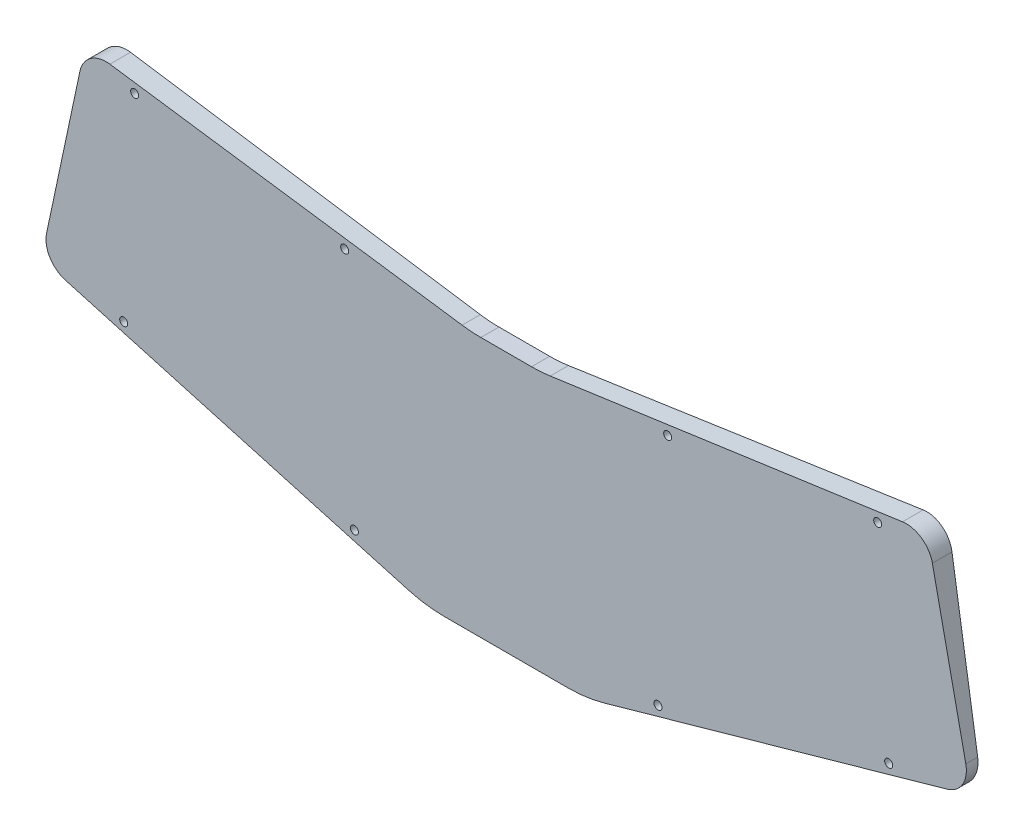
SolidWorks part; units mm, degrees
ref_plane "Front Plane" through (0, 0, 0) normal (0, 0, 1) x (1, 0, 0)
ref_plane "Top Plane" through (0, 0, 0) normal (0, 1, 0) x (1, 0, 0)
ref_plane "Right Plane" through (0, 0, 0) normal (1, 0, 0) x (0, 0, -1)
sketch "Model" plane through (0, 0, 0) normal (0, 0, 1) x (1, 0, 0)
  line L0 (325.3126, 39.9244) -> (319.5653, 66.9637)
  line L1 (325.3126, 39.9244) -> (332.0603, 8.179)
  line L2 (322.3782, 39.3007) -> (316.6308, 66.34)
  line L3 (322.3782, 39.3007) -> (329.1259, 7.5553)
  line L4 (306.4458, 71.4818) -> (308.8024, 71.8155)
  line L5 (13.8071, 71.4818) -> (11.4504, 71.8155)
  line L6 (-5.0598, 39.9244) -> (-11.8075, 8.179)
  line L7 (-2.1254, 39.3007) -> (-8.8731, 7.5553)
  line L8 (-5.0598, 39.9244) -> (0.6876, 66.9637)
  line L9 (-2.1254, 39.3007) -> (3.622, 66.34)
  line L10 (26.3327, -9.1816) -> (48.3039, -15.3856)
  line L11 (48.3039, -15.3856) -> (93.7705, -28.2242)
  line L12 (-3.9283, -0.6367) -> (7.4742, -3.8564)
  line L13 (90.0873, 60.6806) -> (30.9176, 69.0589)
  line L14 (210.7632, 57.9332) -> (177.0346, 53.1572)
  line L15 (169.604, 52.6338) -> (150.6488, 52.6338)
  line L16 (143.2182, 53.1572) -> (109.4896, 57.9332)
  line L17 (289.3352, 69.0589) -> (230.1656, 60.6806)
  line L18 (312.7787, -3.8564) -> (324.1811, -0.6367)
  line L19 (226.4824, -28.2242) -> (271.949, -15.3856)
  line L20 (271.949, -15.3856) -> (293.9202, -9.1816)
  line L21 (112.629, -33.5493) -> (124.2783, -36.8388)
  line L22 (137.0504, -38.6074) -> (160.1264, -38.6074)
  line L23 (160.1264, -38.6074) -> (183.2025, -38.6074)
  line L24 (195.9746, -36.8388) -> (207.6239, -33.5493)
  line L25 (169.604, 55.6338) -> (150.6488, 55.6338)
  line L26 (308.3818, 74.7858) -> (176.614, 56.1276)
  line L27 (272.7642, -18.2727) -> (324.9963, -3.5238)
  line L28 (196.7898, -39.7259) -> (272.7642, -18.2727)
  line L29 (160.1264, -41.6074) -> (183.2025, -41.6074)
  line L30 (137.0504, -41.6074) -> (160.1264, -41.6074)
  line L31 (47.4886, -18.2727) -> (123.463, -39.7259)
  line L32 (-4.7435, -3.5238) -> (47.4886, -18.2727)
  line L33 (143.6388, 56.1276) -> (11.8711, 74.7858)
  line L34 (196.5845, -32.4293) -> (202.5988, -29.3648)
  line L35 (190.1194, -20.2914) -> (196.2483, -32.32)
  line L36 (202.2573, -13.8263) -> (190.2287, -19.9552)
  line L37 (208.7224, -25.9641) -> (202.5935, -13.9355)
  line L38 (202.5988, -29.3648) -> (208.6131, -26.3004)
  line L39 (234.2278, -18.5408) -> (231.421, -5.3358)
  line L40 (220.8303, -21.6441) -> (234.0353, -18.8373)
  line L41 (217.7269, -8.2465) -> (220.5338, -21.4515)
  line L42 (231.1245, -5.1432) -> (217.9195, -7.95)
  line L43 (253.2284, -16.5467) -> (250.4216, -3.3417)
  line L44 (239.8309, -19.6501) -> (253.0359, -16.8433)
  line L45 (236.7276, -6.2525) -> (239.5344, -19.4575)
  line L46 (250.1251, -3.1492) -> (236.9201, -5.956)
  line L47 (210.4452, 1.9626) -> (207.6384, 15.1676)
  line L48 (197.0477, -1.1407) -> (210.2527, 1.6661)
  line L49 (193.9443, 12.2568) -> (196.7512, -0.9482)
  line L50 (207.3419, 15.3602) -> (194.1369, 12.5533)
  line L51 (206.4949, 20.5474) -> (203.6881, 33.7524)
  line L52 (193.0973, 17.4441) -> (206.3023, 20.2509)
  line L53 (189.994, 30.8416) -> (192.8008, 17.6366)
  line L54 (203.3916, 33.945) -> (190.1866, 31.1382)
  line L55 (202.5446, 39.1322) -> (199.7378, 52.3372)
  line L56 (189.147, 36.0289) -> (202.352, 38.8357)
  line L57 (186.0437, 49.4264) -> (188.8505, 36.2214)
  line L58 (199.4413, 52.5298) -> (186.2363, 49.723)
  line L59 (230.2775, 0.044) -> (227.4707, 13.249)
  line L60 (216.8799, -3.0593) -> (230.0849, -0.2525)
  line L61 (213.7766, 10.3383) -> (216.5834, -2.8667)
  line L62 (227.1742, 13.4416) -> (213.9692, 10.6348)
  line L63 (226.3272, 18.6288) -> (223.5204, 31.8338)
  line L64 (212.9296, 15.5255) -> (226.1346, 18.3323)
  line L65 (209.8263, 28.9231) -> (212.6331, 15.7181)
  line L66 (223.2239, 32.0264) -> (210.0189, 29.2196)
  line L67 (222.3769, 37.2136) -> (219.57, 50.4186)
  line L68 (208.9793, 34.1103) -> (222.1843, 36.9171)
  line L69 (205.876, 47.5079) -> (208.6828, 34.3029)
  line L70 (219.2735, 50.6112) -> (206.0685, 47.8044)
  line L71 (249.2781, 2.0381) -> (246.4713, 15.2431)
  line L72 (235.8806, -1.0653) -> (249.0856, 1.7416)
  line L73 (232.7772, 12.3323) -> (235.5841, -0.8727)
  line L74 (246.1748, 15.4356) -> (232.9698, 12.6288)
  line L75 (245.3278, 20.6229) -> (242.521, 33.8279)
  line L76 (231.9302, 17.5195) -> (245.1352, 20.3264)
  line L77 (228.8269, 30.9171) -> (231.6337, 17.7121)
  line L78 (242.2245, 34.0204) -> (229.0195, 31.2136)
  line L79 (241.3775, 39.2077) -> (238.5707, 52.4127)
  line L80 (227.9799, 36.1044) -> (241.1849, 38.9112)
  line L81 (224.8766, 49.5019) -> (227.6834, 36.2969)
  line L82 (238.2742, 52.6052) -> (225.0692, 49.7984)
  line L83 (271.2935, -10.151) -> (268.4867, 3.0539)
  line L84 (257.8959, -13.2544) -> (271.1009, -10.4476)
  line L85 (254.7926, 0.1432) -> (257.5994, -13.0618)
  line L86 (268.1901, 3.2465) -> (254.9852, 0.4397)
  line L87 (267.3431, 8.4338) -> (264.5363, 21.6387)
  line L88 (253.9456, 5.3304) -> (267.1506, 8.1372)
  line L89 (250.8423, 18.728) -> (253.6491, 5.523)
  line L90 (264.2398, 21.8313) -> (251.0348, 19.0245)
  line L91 (263.3928, 27.0186) -> (260.586, 40.2236)
  line L92 (249.9953, 23.9152) -> (263.2003, 26.722)
  line L93 (246.892, 37.3128) -> (249.6988, 24.1078)
  line L94 (260.2895, 40.4161) -> (247.0845, 37.6093)
  line L95 (259.4425, 45.6034) -> (256.6357, 58.8084)
  line L96 (246.045, 42.5) -> (259.2499, 45.3069)
  line L97 (242.9416, 55.8976) -> (245.7484, 42.6926)
  line L98 (256.3392, 59.0009) -> (243.1342, 56.1941)
  line L99 (286.4477, 9.9387) -> (283.6409, 23.1437)
  line L100 (273.0502, 6.8354) -> (286.2552, 9.6422)
  line L101 (269.9469, 20.2329) -> (272.7537, 7.0279)
  line L102 (283.3444, 23.3363) -> (270.1394, 20.5295)
  line L103 (282.4974, 28.5235) -> (279.6906, 41.7285)
  line L104 (269.0999, 25.4202) -> (282.3049, 28.227)
  line L105 (265.9965, 38.8177) -> (268.8033, 25.6128)
  line L106 (279.3941, 41.9211) -> (266.1891, 39.1143)
  line L107 (278.5471, 47.1083) -> (275.7403, 60.3133)
  line L108 (265.1495, 44.005) -> (278.3545, 46.8118)
  line L109 (262.0462, 57.4025) -> (264.853, 44.1976)
  line L110 (275.4438, 60.5059) -> (262.2388, 57.6991)
  line L111 (305.5523, 11.4437) -> (302.7455, 24.6487)
  line L112 (292.1548, 8.3403) -> (305.3598, 11.1471)
  line L113 (289.0514, 21.7379) -> (291.8582, 8.5329)
  line L114 (302.449, 24.8412) -> (289.244, 22.0344)
  line L115 (301.602, 30.0285) -> (298.7952, 43.2335)
  line L116 (288.2044, 26.9251) -> (301.4094, 29.732)
  line L117 (285.1011, 40.3227) -> (287.9079, 27.1177)
  line L118 (298.4987, 43.426) -> (285.2937, 40.6192)
  line L119 (297.6517, 48.6133) -> (294.8449, 61.8183)
  line L120 (284.2541, 45.5099) -> (297.4591, 48.3168)
  line L121 (281.1508, 58.9075) -> (283.9576, 45.7025)
  line L122 (294.5483, 62.0108) -> (281.3434, 59.204)
  line L123 (324.5529, 13.4377) -> (321.7461, 26.6427)
  line L124 (311.1554, 10.3344) -> (324.3604, 13.1412)
  line L125 (308.0521, 23.7319) -> (310.8589, 10.5269)
  line L126 (321.4496, 26.8352) -> (308.2446, 24.0284)
  line L127 (320.6026, 32.0225) -> (317.7958, 45.2275)
  line L128 (307.2051, 28.9192) -> (320.4101, 31.726)
  line L129 (304.1017, 42.3167) -> (306.9086, 29.1117)
  line L130 (317.4993, 45.42) -> (304.2943, 42.6132)
  line L131 (316.6523, 50.6073) -> (313.8455, 63.8123)
  line L132 (313.549, 64.0049) -> (300.344, 61.198)
  line L133 (300.1514, 60.9015) -> (302.9582, 47.6965)
  line L134 (303.2547, 47.504) -> (316.4597, 50.3108)
  line L135 (123.6683, -32.4293) -> (117.654, -29.3648)
  line L136 (130.1334, -20.2914) -> (124.0045, -32.32)
  line L137 (117.9956, -13.8263) -> (130.0242, -19.9552)
  line L138 (111.5305, -25.9641) -> (117.6593, -13.9355)
  line L139 (117.654, -29.3648) -> (111.6397, -26.3004)
  line L140 (86.025, -18.5408) -> (88.8318, -5.3358)
  line L141 (99.4226, -21.6441) -> (86.2176, -18.8373)
  line L142 (102.5259, -8.2465) -> (99.7191, -21.4515)
  line L143 (89.1283, -5.1432) -> (102.3333, -7.95)
  line L144 (67.0244, -16.5467) -> (69.8312, -3.3417)
  line L145 (80.4219, -19.6501) -> (67.2169, -16.8433)
  line L146 (83.5253, -6.2525) -> (80.7184, -19.4575)
  line L147 (70.1277, -3.1492) -> (83.3327, -5.956)
  line L148 (109.8076, 1.9626) -> (112.6144, 15.1676)
  line L149 (123.2052, -1.1407) -> (110.0002, 1.6661)
  line L150 (126.3085, 12.2568) -> (123.5017, -0.9482)
  line L151 (112.9109, 15.3602) -> (126.1159, 12.5533)
  line L152 (113.7579, 20.5474) -> (116.5647, 33.7524)
  line L153 (127.1555, 17.4441) -> (113.9505, 20.2509)
  line L154 (130.2588, 30.8416) -> (127.452, 17.6366)
  line L155 (116.8613, 33.945) -> (130.0662, 31.1382)
  line L156 (117.7083, 39.1322) -> (120.5151, 52.3372)
  line L157 (131.1058, 36.0289) -> (117.9008, 38.8357)
  line L158 (134.2091, 49.4264) -> (131.4023, 36.2214)
  line L159 (120.8116, 52.5298) -> (134.0166, 49.723)
  line L160 (89.9753, 0.044) -> (92.7821, 13.249)
  line L161 (103.3729, -3.0593) -> (90.1679, -0.2525)
  line L162 (106.4762, 10.3383) -> (103.6694, -2.8667)
  line L163 (93.0787, 13.4416) -> (106.2836, 10.6348)
  line L164 (93.9257, 18.6288) -> (96.7325, 31.8338)
  line L165 (107.3232, 15.5255) -> (94.1182, 18.3323)
  line L166 (110.4265, 28.9231) -> (107.6197, 15.7181)
  line L167 (97.029, 32.0264) -> (110.234, 29.2196)
  line L168 (97.876, 37.2136) -> (100.6828, 50.4186)
  line L169 (111.2735, 34.1103) -> (98.0685, 36.9171)
  line L170 (114.3769, 47.5079) -> (111.57, 34.3029)
  line L171 (100.9793, 50.6112) -> (114.1843, 47.8044)
  line L172 (70.9747, 2.0381) -> (73.7815, 15.2431)
  line L173 (84.3723, -1.0653) -> (71.1673, 1.7416)
  line L174 (87.4756, 12.3323) -> (84.6688, -0.8727)
  line L175 (74.078, 15.4356) -> (87.283, 12.6288)
  line L176 (74.925, 20.6229) -> (77.7318, 33.8279)
  line L177 (88.3226, 17.5195) -> (75.1176, 20.3264)
  line L178 (91.4259, 30.9171) -> (88.6191, 17.7121)
  line L179 (78.0284, 34.0204) -> (91.2333, 31.2136)
  line L180 (78.8753, 39.2077) -> (81.6822, 52.4127)
  line L181 (92.2729, 36.1044) -> (79.0679, 38.9112)
  line L182 (95.3762, 49.5019) -> (92.5694, 36.2969)
  line L183 (81.9787, 52.6052) -> (95.1837, 49.7984)
  line L184 (48.9594, -10.151) -> (51.7662, 3.0539)
  line L185 (62.3569, -13.2544) -> (49.1519, -10.4476)
  line L186 (65.4602, 0.1432) -> (62.6534, -13.0618)
  line L187 (52.0627, 3.2465) -> (65.2677, 0.4397)
  line L188 (52.9097, 8.4338) -> (55.7165, 21.6387)
  line L189 (66.3072, 5.3304) -> (53.1022, 8.1372)
  line L190 (69.4106, 18.728) -> (66.6037, 5.523)
  line L191 (56.013, 21.8313) -> (69.218, 19.0245)
  line L192 (56.86, 27.0186) -> (59.6668, 40.2236)
  line L193 (70.2576, 23.9152) -> (57.0526, 26.722)
  line L194 (73.3609, 37.3128) -> (70.5541, 24.1078)
  line L195 (59.9633, 40.4161) -> (73.1683, 37.6093)
  line L196 (60.8103, 45.6034) -> (63.6171, 58.8084)
  line L197 (74.2079, 42.5) -> (61.0029, 45.3069)
  line L198 (77.3112, 55.8976) -> (74.5044, 42.6926)
  line L199 (63.9136, 59.0009) -> (77.1186, 56.1941)
  line L200 (33.8051, 9.9387) -> (36.6119, 23.1437)
  line L201 (47.2026, 6.8354) -> (33.9977, 9.6422)
  line L202 (50.306, 20.2329) -> (47.4992, 7.0279)
  line L203 (36.9084, 23.3363) -> (50.1134, 20.5295)
  line L204 (37.7554, 28.5235) -> (40.5622, 41.7285)
  line L205 (51.153, 25.4202) -> (37.948, 28.227)
  line L206 (54.2563, 38.8177) -> (51.4495, 25.6128)
  line L207 (40.8587, 41.9211) -> (54.0637, 39.1143)
  line L208 (41.7057, 47.1083) -> (44.5125, 60.3133)
  line L209 (55.1033, 44.005) -> (41.8983, 46.8118)
  line L210 (58.2066, 57.4025) -> (55.3998, 44.1976)
  line L211 (44.8091, 60.5059) -> (58.0141, 57.6991)
  line L212 (14.7005, 11.4437) -> (17.5073, 24.6487)
  line L213 (28.0981, 8.3403) -> (14.8931, 11.1471)
  line L214 (31.2014, 21.7379) -> (28.3946, 8.5329)
  line L215 (17.8038, 24.8412) -> (31.0088, 22.0344)
  line L216 (18.6508, 30.0285) -> (21.4576, 43.2335)
  line L217 (32.0484, 26.9251) -> (18.8434, 29.732)
  line L218 (35.1517, 40.3227) -> (32.3449, 27.1177)
  line L219 (21.7542, 43.426) -> (34.9592, 40.6192)
  line L220 (22.6012, 48.6133) -> (25.408, 61.8183)
  line L221 (35.9987, 45.5099) -> (22.7937, 48.3168)
  line L222 (39.102, 58.9075) -> (36.2952, 45.7025)
  line L223 (25.7045, 62.0108) -> (38.9095, 59.204)
  line L224 (-4.3001, 13.4377) -> (-1.4933, 26.6427)
  line L225 (9.0974, 10.3344) -> (-4.1076, 13.1412)
  line L226 (12.2008, 23.7319) -> (9.394, 10.5269)
  line L227 (-1.1968, 26.8352) -> (12.0082, 24.0284)
  line L228 (-0.3498, 32.0225) -> (2.457, 45.2275)
  line L229 (13.0478, 28.9192) -> (-0.1572, 31.726)
  line L230 (16.1511, 42.3167) -> (13.3443, 29.1117)
  line L231 (2.7535, 45.42) -> (15.9585, 42.6132)
  line L232 (3.6005, 50.6073) -> (6.4073, 63.8123)
  line L233 (6.7039, 64.0049) -> (19.9088, 61.198)
  line L234 (20.1014, 60.9015) -> (17.2946, 47.6965)
  line L235 (16.9981, 47.504) -> (3.7931, 50.3108)
  circle A0 centre (21.1464, 69.9376) radius 1.5
  circle A1 centre (299.1065, 69.9376) radius 1.5
  arc A2 (296.6652, 67.2112) -> (289.3352, 69.0589) centre (290.7372, 59.1577) ccw
  arc A3 (306.4458, 71.4818) -> (302.641, 68.6986) centre (307.1468, 66.5312) ccw
  arc A4 (17.6118, 68.6986) -> (13.8071, 71.4818) centre (13.106, 66.5312) ccw
  arc A5 (30.9176, 69.0589) -> (23.5876, 67.2112) centre (29.5156, 59.1577) ccw
  arc A6 (17.6118, 68.6986) -> (23.5876, 67.2112) centre (21.2165, 70.4326) ccw
  arc A7 (296.6652, 67.2112) -> (302.641, 68.6986) centre (299.0364, 70.4326) ccw
  arc A8 (324.9963, -3.5238) -> (332.0603, 8.179) centre (322.2789, 6.0999) ccw
  arc A9 (319.5653, 66.9637) -> (308.3818, 74.7858) centre (309.7838, 64.8846) ccw
  arc A10 (324.1811, -0.6367) -> (329.1259, 7.5553) centre (322.2789, 6.0999) ccw
  arc A11 (316.6308, 66.34) -> (308.8024, 71.8155) centre (309.7838, 64.8846) ccw
  arc A12 (11.8711, 74.7858) -> (0.6876, 66.9637) centre (10.469, 64.8846) ccw
  arc A13 (-11.8075, 8.179) -> (-4.7435, -3.5238) centre (-2.026, 6.0999) ccw
  arc A14 (-8.8731, 7.5553) -> (-3.9283, -0.6367) centre (-2.026, 6.0999) ccw
  arc A15 (11.4504, 71.8155) -> (3.622, 66.34) centre (10.469, 64.8846) ccw
  circle A16 centre (303.2135, -6.0378) radius 1.5
  circle A17 centre (17.0393, -6.0378) radius 1.5
  arc A18 (293.9202, -9.1816) -> (299.8789, -4.5301) centre (291.2027, 0.4421) ccw
  arc A19 (305.2671, -3.0086) -> (312.7787, -3.8564) centre (310.0612, 5.7673) ccw
  arc A20 (20.3739, -4.5301) -> (26.3327, -9.1816) centre (29.0501, 0.4421) ccw
  arc A21 (7.4742, -3.8564) -> (14.9858, -3.0086) centre (10.1916, 5.7673) ccw
  arc A22 (20.3739, -4.5301) -> (14.9858, -3.0086) centre (16.9034, -6.519) ccw
  arc A23 (305.2671, -3.0086) -> (299.8789, -4.5301) centre (303.3494, -6.519) ccw
  circle A24 centre (220.5345, 58.8118) radius 1.5
  circle A25 centre (99.7183, 58.8118) radius 1.5
  arc A26 (230.1656, 60.6806) -> (223.6367, 56.8704) centre (231.5676, 50.7793) ccw
  arc A27 (218.0932, 56.0855) -> (210.7632, 57.9332) centre (212.1652, 48.032) ccw
  arc A28 (96.6161, 56.8704) -> (90.0873, 60.6806) centre (88.6852, 50.7793) ccw
  arc A29 (109.4896, 57.9332) -> (102.1596, 56.0855) centre (108.0876, 48.032) ccw
  arc A30 (218.0932, 56.0855) -> (223.6367, 56.8704) centre (220.4644, 59.3069) ccw
  arc A31 (96.6161, 56.8704) -> (102.1596, 56.0855) centre (99.7884, 59.3069) ccw
  circle A32 centre (216.9173, -30.4056) radius 1.5
  arc A33 (218.9708, -27.3764) -> (226.4824, -28.2242) centre (223.7649, -18.6005) ccw
  arc A34 (207.6239, -33.5493) -> (213.5826, -28.8979) centre (204.9064, -23.9256) ccw
  circle A35 centre (103.3356, -30.4056) radius 1.5
  arc A36 (106.6702, -28.8979) -> (112.629, -33.5493) centre (115.3464, -23.9256) ccw
  arc A37 (93.7705, -28.2242) -> (101.2821, -27.3764) centre (96.4879, -18.6005) ccw
  arc A38 (218.9708, -27.3764) -> (213.5826, -28.8979) centre (217.0531, -30.8868) ccw
  arc A39 (106.6702, -28.8979) -> (101.2821, -27.3764) centre (103.1997, -30.8868) ccw
  arc A40 (169.604, 55.6338) -> (176.614, 56.1276) centre (169.604, 105.6338) ccw
  arc A41 (183.2025, -41.6074) -> (196.7898, -39.7259) centre (183.2025, 8.3926) ccw
  arc A42 (123.463, -39.7259) -> (137.0504, -41.6074) centre (137.0504, 8.3926) ccw
  arc A43 (143.6388, 56.1276) -> (150.6488, 55.6338) centre (150.6488, 105.6338) ccw
  arc A44 (196.2483, -32.32) -> (196.5845, -32.4293) centre (196.471, -32.2065) ccw
  arc A45 (190.2287, -19.9552) -> (190.1194, -20.2914) centre (190.3422, -20.1779) ccw
  arc A46 (202.5935, -13.9355) -> (202.2573, -13.8263) centre (202.3708, -14.049) ccw
  arc A47 (208.6131, -26.3004) -> (208.7224, -25.9641) centre (208.4996, -26.0776) ccw
  arc A48 (231.421, -5.3358) -> (231.1245, -5.1432) centre (231.1765, -5.3878) ccw
  arc A49 (217.9195, -7.95) -> (217.7269, -8.2465) centre (217.9715, -8.1946) ccw
  arc A50 (220.5338, -21.4515) -> (220.8303, -21.6441) centre (220.7783, -21.3996) ccw
  arc A51 (234.0353, -18.8373) -> (234.2278, -18.5408) centre (233.9833, -18.5927) ccw
  arc A52 (250.4216, -3.3417) -> (250.1251, -3.1492) centre (250.1771, -3.3937) ccw
  arc A53 (236.9201, -5.956) -> (236.7276, -6.2525) centre (236.9721, -6.2005) ccw
  arc A54 (239.5344, -19.4575) -> (239.8309, -19.6501) centre (239.7789, -19.4055) ccw
  arc A55 (253.0359, -16.8433) -> (253.2284, -16.5467) centre (252.9839, -16.5987) ccw
  arc A56 (207.6384, 15.1676) -> (207.3419, 15.3602) centre (207.3939, 15.1156) ccw
  arc A57 (194.1369, 12.5533) -> (193.9443, 12.2568) centre (194.1889, 12.3088) ccw
  arc A58 (196.7512, -0.9482) -> (197.0477, -1.1407) centre (196.9957, -0.8962) ccw
  arc A59 (210.2527, 1.6661) -> (210.4452, 1.9626) centre (210.2007, 1.9106) ccw
  arc A60 (203.6881, 33.7524) -> (203.3916, 33.945) centre (203.4436, 33.7004) ccw
  arc A61 (190.1866, 31.1382) -> (189.994, 30.8416) centre (190.2386, 30.8936) ccw
  arc A62 (192.8008, 17.6366) -> (193.0973, 17.4441) centre (193.0454, 17.6886) ccw
  arc A63 (206.3023, 20.2509) -> (206.4949, 20.5474) centre (206.2504, 20.4954) ccw
  arc A64 (199.7378, 52.3372) -> (199.4413, 52.5298) centre (199.4932, 52.2852) ccw
  arc A65 (186.2363, 49.723) -> (186.0437, 49.4264) centre (186.2882, 49.4784) ccw
  arc A66 (188.8505, 36.2214) -> (189.147, 36.0289) centre (189.095, 36.2734) ccw
  arc A67 (202.352, 38.8357) -> (202.5446, 39.1322) centre (202.3, 39.0802) ccw
  arc A68 (227.4707, 13.249) -> (227.1742, 13.4416) centre (227.2262, 13.1971) ccw
  arc A69 (213.9692, 10.6348) -> (213.7766, 10.3383) centre (214.0212, 10.3902) ccw
  arc A70 (216.5834, -2.8667) -> (216.8799, -3.0593) centre (216.828, -2.8147) ccw
  arc A71 (230.0849, -0.2525) -> (230.2775, 0.044) centre (230.033, -0.0079) ccw
  arc A72 (223.5204, 31.8338) -> (223.2239, 32.0264) centre (223.2758, 31.7819) ccw
  arc A73 (210.0189, 29.2196) -> (209.8263, 28.9231) centre (210.0708, 28.9751) ccw
  arc A74 (212.6331, 15.7181) -> (212.9296, 15.5255) centre (212.8776, 15.7701) ccw
  arc A75 (226.1346, 18.3323) -> (226.3272, 18.6288) centre (226.0826, 18.5769) ccw
  arc A76 (219.57, 50.4186) -> (219.2735, 50.6112) centre (219.3255, 50.3667) ccw
  arc A77 (206.0685, 47.8044) -> (205.876, 47.5079) centre (206.1205, 47.5599) ccw
  arc A78 (208.6828, 34.3029) -> (208.9793, 34.1103) centre (208.9273, 34.3549) ccw
  arc A79 (222.1843, 36.9171) -> (222.3769, 37.2136) centre (222.1323, 37.1617) ccw
  arc A80 (246.4713, 15.2431) -> (246.1748, 15.4356) centre (246.2268, 15.1911) ccw
  arc A81 (249.0856, 1.7416) -> (249.2781, 2.0381) centre (249.0336, 1.9861) ccw
  arc A82 (232.9698, 12.6288) -> (232.7772, 12.3323) centre (233.0218, 12.3843) ccw
  arc A83 (235.5841, -0.8727) -> (235.8806, -1.0653) centre (235.8286, -0.8207) ccw
  arc A84 (242.521, 33.8279) -> (242.2245, 34.0204) centre (242.2765, 33.7759) ccw
  arc A85 (229.0195, 31.2136) -> (228.8269, 30.9171) centre (229.0715, 30.9691) ccw
  arc A86 (231.6337, 17.7121) -> (231.9302, 17.5195) centre (231.8783, 17.7641) ccw
  arc A87 (245.1352, 20.3264) -> (245.3278, 20.6229) centre (245.0833, 20.5709) ccw
  arc A88 (238.5707, 52.4127) -> (238.2742, 52.6052) centre (238.3261, 52.3607) ccw
  arc A89 (225.0692, 49.7984) -> (224.8766, 49.5019) centre (225.1211, 49.5539) ccw
  arc A90 (227.6834, 36.2969) -> (227.9799, 36.1044) centre (227.9279, 36.3489) ccw
  arc A91 (241.1849, 38.9112) -> (241.3775, 39.2077) centre (241.1329, 39.1557) ccw
  arc A92 (268.4867, 3.0539) -> (268.1901, 3.2465) centre (268.2421, 3.002) ccw
  arc A93 (254.9852, 0.4397) -> (254.7926, 0.1432) centre (255.0371, 0.1952) ccw
  arc A94 (257.5994, -13.0618) -> (257.8959, -13.2544) centre (257.8439, -13.0098) ccw
  arc A95 (271.1009, -10.4476) -> (271.2935, -10.151) centre (271.0489, -10.203) ccw
  arc A96 (264.5363, 21.6387) -> (264.2398, 21.8313) centre (264.2918, 21.5868) ccw
  arc A97 (251.0348, 19.0245) -> (250.8423, 18.728) centre (251.0868, 18.78) ccw
  arc A98 (253.6491, 5.523) -> (253.9456, 5.3304) centre (253.8936, 5.575) ccw
  arc A99 (267.1506, 8.1372) -> (267.3431, 8.4338) centre (267.0986, 8.3818) ccw
  arc A100 (260.586, 40.2236) -> (260.2895, 40.4161) centre (260.3415, 40.1716) ccw
  arc A101 (247.0845, 37.6093) -> (246.892, 37.3128) centre (247.1365, 37.3648) ccw
  arc A102 (249.6988, 24.1078) -> (249.9953, 23.9152) centre (249.9433, 24.1598) ccw
  arc A103 (263.2003, 26.722) -> (263.3928, 27.0186) centre (263.1483, 26.9666) ccw
  arc A104 (256.6357, 58.8084) -> (256.3392, 59.0009) centre (256.3912, 58.7564) ccw
  arc A105 (243.1342, 56.1941) -> (242.9416, 55.8976) centre (243.1862, 55.9496) ccw
  arc A106 (245.7484, 42.6926) -> (246.045, 42.5) centre (245.993, 42.7446) ccw
  arc A107 (259.2499, 45.3069) -> (259.4425, 45.6034) centre (259.198, 45.5514) ccw
  arc A108 (283.6409, 23.1437) -> (283.3444, 23.3363) centre (283.3964, 23.0917) ccw
  arc A109 (270.1394, 20.5295) -> (269.9469, 20.2329) centre (270.1914, 20.2849) ccw
  arc A110 (272.7537, 7.0279) -> (273.0502, 6.8354) centre (272.9982, 7.0799) ccw
  arc A111 (286.2552, 9.6422) -> (286.4477, 9.9387) centre (286.2032, 9.8867) ccw
  arc A112 (279.6906, 41.7285) -> (279.3941, 41.9211) centre (279.4461, 41.6765) ccw
  arc A113 (266.1891, 39.1143) -> (265.9965, 38.8177) centre (266.2411, 38.8697) ccw
  arc A114 (268.8033, 25.6128) -> (269.0999, 25.4202) centre (269.0479, 25.6647) ccw
  arc A115 (282.3049, 28.227) -> (282.4974, 28.5235) centre (282.2529, 28.4715) ccw
  arc A116 (275.7403, 60.3133) -> (275.4438, 60.5059) centre (275.4957, 60.2613) ccw
  arc A117 (262.2388, 57.6991) -> (262.0462, 57.4025) centre (262.2908, 57.4545) ccw
  arc A118 (264.853, 44.1976) -> (265.1495, 44.005) centre (265.0976, 44.2495) ccw
  arc A119 (278.3545, 46.8118) -> (278.5471, 47.1083) centre (278.3026, 47.0563) ccw
  arc A120 (302.7455, 24.6487) -> (302.449, 24.8412) centre (302.501, 24.5967) ccw
  arc A121 (305.3598, 11.1471) -> (305.5523, 11.4437) centre (305.3078, 11.3917) ccw
  arc A122 (289.244, 22.0344) -> (289.0514, 21.7379) centre (289.296, 21.7899) ccw
  arc A123 (291.8582, 8.5329) -> (292.1548, 8.3403) centre (292.1028, 8.5849) ccw
  arc A124 (298.7952, 43.2335) -> (298.4987, 43.426) centre (298.5506, 43.1815) ccw
  arc A125 (285.2937, 40.6192) -> (285.1011, 40.3227) centre (285.3457, 40.3747) ccw
  arc A126 (287.9079, 27.1177) -> (288.2044, 26.9251) centre (288.1525, 27.1697) ccw
  arc A127 (301.4094, 29.732) -> (301.602, 30.0285) centre (301.3575, 29.9765) ccw
  arc A128 (294.8449, 61.8183) -> (294.5483, 62.0108) centre (294.6003, 61.7663) ccw
  arc A129 (281.3434, 59.204) -> (281.1508, 58.9075) centre (281.3953, 58.9595) ccw
  arc A130 (283.9576, 45.7025) -> (284.2541, 45.5099) centre (284.2021, 45.7545) ccw
  arc A131 (297.4591, 48.3168) -> (297.6517, 48.6133) centre (297.4071, 48.5613) ccw
  arc A132 (321.7461, 26.6427) -> (321.4496, 26.8352) centre (321.5016, 26.5907) ccw
  arc A133 (308.2446, 24.0284) -> (308.0521, 23.7319) centre (308.2966, 23.7839) ccw
  arc A134 (310.8589, 10.5269) -> (311.1554, 10.3344) centre (311.1034, 10.5789) ccw
  arc A135 (324.3604, 13.1412) -> (324.5529, 13.4377) centre (324.3084, 13.3857) ccw
  arc A136 (317.7958, 45.2275) -> (317.4993, 45.42) centre (317.5513, 45.1755) ccw
  arc A137 (306.9086, 29.1117) -> (307.2051, 28.9192) centre (307.1531, 29.1637) ccw
  arc A138 (320.4101, 31.726) -> (320.6026, 32.0225) centre (320.3581, 31.9705) ccw
  arc A139 (304.2943, 42.6132) -> (304.1017, 42.3167) centre (304.3463, 42.3687) ccw
  arc A140 (313.8455, 63.8123) -> (313.549, 64.0049) centre (313.601, 63.7603) ccw
  arc A141 (300.344, 61.198) -> (300.1514, 60.9015) centre (300.396, 60.9535) ccw
  arc A142 (316.4597, 50.3108) -> (316.6523, 50.6073) centre (316.4078, 50.5553) ccw
  arc A143 (302.9582, 47.6965) -> (303.2547, 47.504) centre (303.2028, 47.7485) ccw
  arc A144 (123.6683, -32.4293) -> (124.0045, -32.32) centre (123.7818, -32.2065) ccw
  arc A145 (130.1334, -20.2914) -> (130.0242, -19.9552) centre (129.9107, -20.1779) ccw
  arc A146 (117.9956, -13.8263) -> (117.6593, -13.9355) centre (117.8821, -14.049) ccw
  arc A147 (111.5305, -25.9641) -> (111.6397, -26.3004) centre (111.7532, -26.0776) ccw
  arc A148 (89.1283, -5.1432) -> (88.8318, -5.3358) centre (89.0764, -5.3878) ccw
  arc A149 (102.5259, -8.2465) -> (102.3333, -7.95) centre (102.2813, -8.1946) ccw
  arc A150 (99.4226, -21.6441) -> (99.7191, -21.4515) centre (99.4745, -21.3996) ccw
  arc A151 (86.025, -18.5408) -> (86.2176, -18.8373) centre (86.2695, -18.5927) ccw
  arc A152 (70.1277, -3.1492) -> (69.8312, -3.3417) centre (70.0757, -3.3937) ccw
  arc A153 (83.5253, -6.2525) -> (83.3327, -5.956) centre (83.2807, -6.2005) ccw
  arc A154 (80.4219, -19.6501) -> (80.7184, -19.4575) centre (80.4739, -19.4055) ccw
  arc A155 (67.0244, -16.5467) -> (67.2169, -16.8433) centre (67.2689, -16.5987) ccw
  arc A156 (112.9109, 15.3602) -> (112.6144, 15.1676) centre (112.859, 15.1156) ccw
  arc A157 (126.3085, 12.2568) -> (126.1159, 12.5533) centre (126.0639, 12.3088) ccw
  arc A158 (123.2052, -1.1407) -> (123.5017, -0.9482) centre (123.2571, -0.8962) ccw
  arc A159 (109.8076, 1.9626) -> (110.0002, 1.6661) centre (110.0521, 1.9106) ccw
  arc A160 (116.8613, 33.945) -> (116.5647, 33.7524) centre (116.8093, 33.7004) ccw
  arc A161 (130.2588, 30.8416) -> (130.0662, 31.1382) centre (130.0143, 30.8936) ccw
  arc A162 (127.1555, 17.4441) -> (127.452, 17.6366) centre (127.2075, 17.6886) ccw
  arc A163 (113.7579, 20.5474) -> (113.9505, 20.2509) centre (114.0025, 20.4954) ccw
  arc A164 (120.8116, 52.5298) -> (120.5151, 52.3372) centre (120.7596, 52.2852) ccw
  arc A165 (134.2091, 49.4264) -> (134.0166, 49.723) centre (133.9646, 49.4784) ccw
  arc A166 (131.1058, 36.0289) -> (131.4023, 36.2214) centre (131.1578, 36.2734) ccw
  arc A167 (117.7083, 39.1322) -> (117.9008, 38.8357) centre (117.9528, 39.0802) ccw
  arc A168 (93.0787, 13.4416) -> (92.7821, 13.249) centre (93.0267, 13.1971) ccw
  arc A169 (106.4762, 10.3383) -> (106.2836, 10.6348) centre (106.2317, 10.3902) ccw
  arc A170 (103.3729, -3.0593) -> (103.6694, -2.8667) centre (103.4249, -2.8147) ccw
  arc A171 (89.9753, 0.044) -> (90.1679, -0.2525) centre (90.2199, -0.0079) ccw
  arc A172 (97.029, 32.0264) -> (96.7325, 31.8338) centre (96.977, 31.7819) ccw
  arc A173 (110.4265, 28.9231) -> (110.234, 29.2196) centre (110.182, 28.9751) ccw
  arc A174 (107.3232, 15.5255) -> (107.6197, 15.7181) centre (107.3752, 15.7701) ccw
  arc A175 (93.9257, 18.6288) -> (94.1182, 18.3323) centre (94.1702, 18.5769) ccw
  arc A176 (100.9793, 50.6112) -> (100.6828, 50.4186) centre (100.9273, 50.3667) ccw
  arc A177 (114.3769, 47.5079) -> (114.1843, 47.8044) centre (114.1323, 47.5599) ccw
  arc A178 (111.2735, 34.1103) -> (111.57, 34.3029) centre (111.3255, 34.3549) ccw
  arc A179 (97.876, 37.2136) -> (98.0685, 36.9171) centre (98.1205, 37.1617) ccw
  arc A180 (74.078, 15.4356) -> (73.7815, 15.2431) centre (74.026, 15.1911) ccw
  arc A181 (70.9747, 2.0381) -> (71.1673, 1.7416) centre (71.2192, 1.9861) ccw
  arc A182 (87.4756, 12.3323) -> (87.283, 12.6288) centre (87.231, 12.3843) ccw
  arc A183 (84.3723, -1.0653) -> (84.6688, -0.8727) centre (84.4242, -0.8207) ccw
  arc A184 (78.0284, 34.0204) -> (77.7318, 33.8279) centre (77.9764, 33.7759) ccw
  arc A185 (91.4259, 30.9171) -> (91.2333, 31.2136) centre (91.1814, 30.9691) ccw
  arc A186 (88.3226, 17.5195) -> (88.6191, 17.7121) centre (88.3746, 17.7641) ccw
  arc A187 (74.925, 20.6229) -> (75.1176, 20.3264) centre (75.1696, 20.5709) ccw
  arc A188 (81.9787, 52.6052) -> (81.6822, 52.4127) centre (81.9267, 52.3607) ccw
  arc A189 (95.3762, 49.5019) -> (95.1837, 49.7984) centre (95.1317, 49.5539) ccw
  arc A190 (92.2729, 36.1044) -> (92.5694, 36.2969) centre (92.3249, 36.3489) ccw
  arc A191 (78.8753, 39.2077) -> (79.0679, 38.9112) centre (79.1199, 39.1557) ccw
  arc A192 (52.0627, 3.2465) -> (51.7662, 3.0539) centre (52.0107, 3.002) ccw
  arc A193 (65.4602, 0.1432) -> (65.2677, 0.4397) centre (65.2157, 0.1952) ccw
  arc A194 (62.3569, -13.2544) -> (62.6534, -13.0618) centre (62.4089, -13.0098) ccw
  arc A195 (48.9594, -10.151) -> (49.1519, -10.4476) centre (49.2039, -10.203) ccw
  arc A196 (56.013, 21.8313) -> (55.7165, 21.6387) centre (55.961, 21.5868) ccw
  arc A197 (69.4106, 18.728) -> (69.218, 19.0245) centre (69.166, 18.78) ccw
  arc A198 (66.3072, 5.3304) -> (66.6037, 5.523) centre (66.3592, 5.575) ccw
  arc A199 (52.9097, 8.4338) -> (53.1022, 8.1372) centre (53.1542, 8.3818) ccw
  arc A200 (59.9633, 40.4161) -> (59.6668, 40.2236) centre (59.9113, 40.1716) ccw
  arc A201 (73.3609, 37.3128) -> (73.1683, 37.6093) centre (73.1163, 37.3648) ccw
  arc A202 (70.2576, 23.9152) -> (70.5541, 24.1078) centre (70.3095, 24.1598) ccw
  arc A203 (56.86, 27.0186) -> (57.0526, 26.722) centre (57.1045, 26.9666) ccw
  arc A204 (63.9136, 59.0009) -> (63.6171, 58.8084) centre (63.8617, 58.7564) ccw
  arc A205 (77.3112, 55.8976) -> (77.1186, 56.1941) centre (77.0667, 55.9496) ccw
  arc A206 (74.2079, 42.5) -> (74.5044, 42.6926) centre (74.2599, 42.7446) ccw
  arc A207 (60.8103, 45.6034) -> (61.0029, 45.3069) centre (61.0549, 45.5514) ccw
  arc A208 (36.9084, 23.3363) -> (36.6119, 23.1437) centre (36.8564, 23.0917) ccw
  arc A209 (50.306, 20.2329) -> (50.1134, 20.5295) centre (50.0614, 20.2849) ccw
  arc A210 (47.2026, 6.8354) -> (47.4992, 7.0279) centre (47.2546, 7.0799) ccw
  arc A211 (33.8051, 9.9387) -> (33.9977, 9.6422) centre (34.0496, 9.8867) ccw
  arc A212 (40.8587, 41.9211) -> (40.5622, 41.7285) centre (40.8068, 41.6765) ccw
  arc A213 (54.2563, 38.8177) -> (54.0637, 39.1143) centre (54.0118, 38.8697) ccw
  arc A214 (51.153, 25.4202) -> (51.4495, 25.6128) centre (51.2049, 25.6647) ccw
  arc A215 (37.7554, 28.5235) -> (37.948, 28.227) centre (38, 28.4715) ccw
  arc A216 (44.8091, 60.5059) -> (44.5125, 60.3133) centre (44.7571, 60.2613) ccw
  arc A217 (58.2066, 57.4025) -> (58.0141, 57.6991) centre (57.9621, 57.4545) ccw
  arc A218 (55.1033, 44.005) -> (55.3998, 44.1976) centre (55.1553, 44.2495) ccw
  arc A219 (41.7057, 47.1083) -> (41.8983, 46.8118) centre (41.9503, 47.0563) ccw
  arc A220 (17.8038, 24.8412) -> (17.5073, 24.6487) centre (17.7519, 24.5967) ccw
  arc A221 (14.7005, 11.4437) -> (14.8931, 11.1471) centre (14.945, 11.3917) ccw
  arc A222 (31.2014, 21.7379) -> (31.0088, 22.0344) centre (30.9569, 21.7899) ccw
  arc A223 (28.0981, 8.3403) -> (28.3946, 8.5329) centre (28.15, 8.5849) ccw
  arc A224 (21.7542, 43.426) -> (21.4576, 43.2335) centre (21.7022, 43.1815) ccw
  arc A225 (35.1517, 40.3227) -> (34.9592, 40.6192) centre (34.9072, 40.3747) ccw
  arc A226 (32.0484, 26.9251) -> (32.3449, 27.1177) centre (32.1004, 27.1697) ccw
  arc A227 (18.6508, 30.0285) -> (18.8434, 29.732) centre (18.8954, 29.9765) ccw
  arc A228 (25.7045, 62.0108) -> (25.408, 61.8183) centre (25.6525, 61.7663) ccw
  arc A229 (39.102, 58.9075) -> (38.9095, 59.204) centre (38.8575, 58.9595) ccw
  arc A230 (35.9987, 45.5099) -> (36.2952, 45.7025) centre (36.0507, 45.7545) ccw
  arc A231 (22.6012, 48.6133) -> (22.7937, 48.3168) centre (22.8457, 48.5613) ccw
  arc A232 (-1.1968, 26.8352) -> (-1.4933, 26.6427) centre (-1.2488, 26.5907) ccw
  arc A233 (12.2008, 23.7319) -> (12.0082, 24.0284) centre (11.9562, 23.7839) ccw
  arc A234 (9.0974, 10.3344) -> (9.394, 10.5269) centre (9.1494, 10.5789) ccw
  arc A235 (-4.3001, 13.4377) -> (-4.1076, 13.1412) centre (-4.0556, 13.3857) ccw
  arc A236 (2.7535, 45.42) -> (2.457, 45.2275) centre (2.7016, 45.1755) ccw
  arc A237 (13.0478, 28.9192) -> (13.3443, 29.1117) centre (13.0997, 29.1637) ccw
  arc A238 (-0.3498, 32.0225) -> (-0.1572, 31.726) centre (-0.1053, 31.9705) ccw
  arc A239 (16.1511, 42.3167) -> (15.9585, 42.6132) centre (15.9065, 42.3687) ccw
  arc A240 (6.7039, 64.0049) -> (6.4073, 63.8123) centre (6.6519, 63.7603) ccw
  arc A241 (20.1014, 60.9015) -> (19.9088, 61.198) centre (19.8569, 60.9535) ccw
  arc A242 (3.6005, 50.6073) -> (3.7931, 50.3108) centre (3.8451, 50.5553) ccw
  arc A243 (16.9981, 47.504) -> (17.2946, 47.6965) centre (17.0501, 47.7485) ccw
  arc A244 (169.604, 52.6338) -> (177.0346, 53.1572) centre (169.604, 105.6338) ccw
  arc A245 (143.2182, 53.1572) -> (150.6488, 52.6338) centre (150.6488, 105.6338) ccw
  arc A246 (124.2783, -36.8388) -> (137.0504, -38.6074) centre (137.0504, 8.3926) ccw
  arc A247 (183.2025, -38.6074) -> (195.9746, -36.8388) centre (183.2025, 8.3926) ccw
extrude "Boss-Extrude1" add sketch "Model" along normal blind 8 contours L23 A247 L24 A34 A38 A33 L19 L20 A18 A23 A19 L18 A10 L3 L2 A11 L4 A3 A7 A2 L17 A26 A30 A27 L14 A244 L15 A245 L16 A29 A31 A28 L13 A5 A6 A4 L5 A15 L9 L7 A14 L12 A21 A22 A20 L10 L11 A37 A39 A36 L21 | A43 L33 A12 L8 L6 A13 L32 L31 A42 L30 L29 A41 L28 L27 A8 L1 L0 A9 L26 A40 L25 A247 L23 L22 A246 L21 A36 A39 A37 L11 L10 A20 A22 A21 L12 A14 L7 L9 A15 L5 A4 A6 A5 L13 A28 A31 A29 L16 A245 L15 | L235 A243 L234 A241 L233 A240 L232 A242 | L220 A231 L221 A230 L222 A229 L223 A228 | L216 A227 L217 A226 L218 A225 L219 A224 | L230 A239 L231 A236 L228 A238 L229 A237 | L224 A235 L225 A234 L226 A233 L227 A232 | L213 A223 L214 A222 L215 A220 L212 A221 | L200 A211 L201 A210 L202 A209 L203 A208 | L204 A215 L205 A214 L206 A213 L207 A212 | L208 A219 L209 A218 L210 A217 L211 A216 | L196 A207 L197 A206 L198 A205 L199 A204 | L192 A203 L193 A202 L194 A201 L195 A200 | L188 A199 L189 A198 L190 A197 L191 A196 | L184 A195 L185 A194 L186 A193 L187 A192 | L144 A155 L145 A154 L146 A153 L147 A152 | L140 A151 L141 A150 L142 A149 L143 A148 | L160 A171 L161 A170 L162 A169 L163 A168 | L173 A183 L174 A182 L175 A180 L172 A181 | L176 A187 L177 A186 L178 A185 L179 A184 | L180 A191 L181 A190 L182 A189 L183 A188 | L168 A179 L169 A178 L170 A177 L171 A176 | L152 A163 L153 A162 L154 A161 L155 A160 | L148 A159 L149 A158 L150 A157 L151 A156 | L138 A147 L139 L135 A144 L136 A145 L137 A146 | L164 A175 L165 A174 L166 A173 L167 A172 | L156 A167 L157 A166 L158 A165 L159 A164 | L56 A67 L55 A64 L58 A65 L57 A66 | L52 A63 L51 A60 L54 A61 L53 A62 | L48 A59 L47 A56 L50 A57 L49 A58 | L38 A47 L37 A46 L36 A45 L35 A44 L34 | L40 A51 L39 A48 L42 A49 L41 A50 | L44 A55 L43 A52 L46 A53 L45 A54 | L84 A95 L83 A92 L86 A93 L85 A94 | L88 A99 L87 A96 L90 A97 L89 A98 | L73 A83 L72 A81 L71 A80 L74 A82 | L60 A71 L59 A68 L62 A69 L61 A70 | L64 A75 L63 A72 L66 A73 L65 A74 | L68 A79 L67 A76 L70 A77 L69 A78 | L80 A91 L79 A88 L82 A89 L81 A90 | L76 A87 L75 A84 L78 A85 L77 A86 | L92 A103 L91 A100 L94 A101 L93 A102 | L96 A107 L95 A104 L98 A105 L97 A106 | L108 A119 L107 A116 L110 A117 L109 A118 | L104 A115 L103 A112 L106 A113 L105 A114 | L100 A111 L99 A108 L102 A109 L101 A110 | L113 A123 L112 A121 L111 A120 L114 A122 | L116 A127 L115 A124 L118 A125 L117 A126 | L120 A131 L119 A128 L122 A129 L121 A130 | L133 A143 L134 A142 L131 A140 L132 A141 | L130 A139 L129 A137 L128 A138 L127 A136 | L124 A135 L123 A132 L126 A133 L125 A134 region at (328.331, 23.9762, 0) region at (160.1264, 15.5989, 0) region at (199.4209, -23.1278, 0) region at (225.9774, -13.3937, 0) region at (244.978, -11.3996, 0) region at (202.1948, 7.1097, 0) region at (198.2445, 25.6945, 0) region at (194.2941, 44.2793, 0) region at (222.0271, 5.1912, 0) region at (218.0767, 23.776, 0) region at (214.1264, 42.3608, 0) region at (241.0277, 7.1852, 0) region at (237.0774, 25.77, 0) region at (233.127, 44.3548, 0) region at (263.043, -5.0039, 0) region at (259.0927, 13.5809, 0) region at (255.1424, 32.1657, 0) region at (251.1921, 50.7505, 0) region at (278.1973, 15.0858, 0) region at (274.247, 33.6706, 0) region at (270.2967, 52.2554, 0) region at (297.3019, 16.5908, 0) region at (293.3516, 35.1756, 0) region at (289.4012, 53.7604, 0) region at (316.3025, 18.5848, 0) region at (312.3522, 37.1696, 0) region at (308.4019, 55.7544, 0) region at (120.8319, -23.1278, 0) region at (94.2754, -13.3937, 0) region at (75.2748, -11.3996, 0) region at (118.058, 7.1097, 0) region at (122.0084, 25.6945, 0) region at (125.9587, 44.2793, 0) region at (98.2258, 5.1912, 0) region at (102.1761, 23.776, 0) region at (106.1264, 42.3608, 0) region at (79.2251, 7.1852, 0) region at (83.1755, 25.77, 0) region at (87.1258, 44.3548, 0) region at (57.2098, -5.0039, 0) region at (61.1601, 13.5809, 0) region at (65.1104, 32.1657, 0) region at (69.0608, 50.7505, 0) region at (42.0555, 15.0858, 0) region at (46.0059, 33.6706, 0) region at (49.9562, 52.2554, 0) region at (22.9509, 16.5908, 0) region at (26.9013, 35.1756, 0) region at (30.8516, 53.7604, 0) region at (3.9503, 18.5848, 0) region at (7.9006, 37.1696, 0) region at (11.851, 55.7544, 0)
extrude "Boss-Extrude2" add sketch "Model<3>" along normal blind 8 contours A43 L33 A12 L8 L6 A13 L32 L31 A42 L30 L29 A41 L28 L27 A8 L1 L0 A9 L26 A40 L25 A247 L23 L22 A246 L21 A36 A39 A37 L11 L10 A20 A22 A21 L12 A14 L7 L9 A15 L5 A4 A6 A5 L13 A28 A31 A29 L16 A245 L15 region at (328.331, 23.9762, 0)
sketch "Model<3>" plane through (0, 0, 0) normal (0, 0, 1) x (1, 0, 0) same geometry as "Model"
sketch "Sketch2" plane through (0, 0, 0) normal (1, 0, 0) x (0, 0, -1)
  line L0 (0, 80.5211) -> (0, -41.6074)
  line L1 (0, -41.6074) -> (-8, -41.6074)
  line L3 (-8, -41.6074) -> (-6, -41.6074)
  line L4 (-6, -41.6074) -> (0, 80.5211)
extrude "Cut-Extrude2" cut sketch "Sketch2" against normal through all both and the other way through all contours L4 L1 L0 region at (0, -0.8979, 2)
